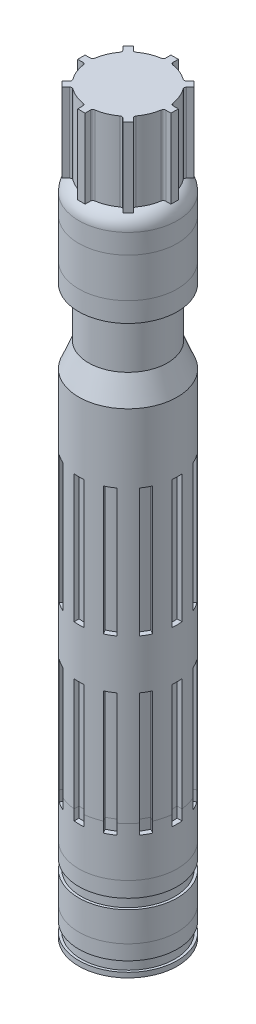
SolidWorks part; units mm, degrees
material "AISI 8620 Steel, carburized"
ref_plane "Front Plane" through (0, 0, 0) normal (1, 0, 0) x (0, 1, 0)
ref_plane "Top Plane" through (0, 0, 0) normal (0, 0, 1) x (0, 1, 0)
ref_plane "Right Plane" through (0, 0, 0) normal (0, 1, 0) x (-1, 0, 0)
sketch "Sketch1" plane through (0, 0, 0) normal (1, 0, 0) x (0, 1, 0)
  line L0 (0, 18.7749) -> (0, 0) construction
  line L1 (-96.0799, 0) -> (122.7259, 0) construction
  line L2 (-70, 0) -> (-70, 10)
  line L3 (-70, 10) -> (30, 10)
  line L4 (70, 8) -> (70, 0) construction
  line L5 (30, 10) -> (30, 0)
  line L6 (35, 8) -> (30, 10)
  line L7 (45, 10) -> (45, 0)
  line L8 (35, 8) -> (45, 8)
  line L9 (45, 10) -> (61, 10)
  line L10 (61, 10) -> (61, 0)
  line L11 (64, 8) -> (70, 8)
  line L12 (64, 8) -> (64, 0)
  line L13 (80, 8) -> (80, 0)
  line L14 (70, 8) -> (80, 8)
  line L15 (-70, 0) -> (80, 0)
  line L16 (-69, 10) -> (-69, 0)
  line L17 (-67, 10) -> (-67, 0)
  line L18 (-58, 10) -> (-58, 0)
  line L19 (-56, 10) -> (-56, 0)
  line L20 (-69, 9.5) -> (-67, 9.5)
  line L21 (-58, 10) -> (-56, 10)
  line L22 (-58, 9.5) -> (-56, 9.5)
  line L23 (35, 8) -> (35, 0)
  arc A0 (61, 10) -> (64, 8) centre (61, 6.75) cw
  dimension "D12" = 3.25
  dimension "D1" = 20
  dimension "D2" = 140
  dimension "D3" = 70
  dimension "D4" = 15
  dimension "D5" = 100
  dimension "D6" = 10
  dimension "D7" = 16
  dimension "D8" = 20
  dimension "D9" = 9
  dimension "D10" = 3
  dimension "D11" = 10
  dimension "D13" = 2
  dimension "D14" = 2
  dimension "D15" = 19
  dimension "D16" = 1
  dimension "D18" = 8
  dimension "D17" = 14
revolve "Revolve1" add sketch "Sketch1" angle 360 about L1 region at (0, -69.5, 5) region at (0, -68, 4.75) region at (0, -62.5, 5) region at (0, -57, 4.75) region at (0, -13, 5) region at (0, 32.4074, 4.5185) region at (0, 40, 4) region at (0, 53, 5) region at (0, 62.4528, 4.7384) region at (0, 72, 4)
sketch "Sketch2" plane through (0, 0, 0) normal (1, 0, 0) x (0, 1, 0)
  line L0 (-13.6637, 0) -> (10.2751, 0) construction
  line L1 (-45, 1) -> (-20, 1)
  line L2 (-45, 1) -> (-45, -1)
  line L3 (-45, -1) -> (-20, -1)
  line L4 (-20, 1) -> (-20, -1)
  line L5 (-70, 10) -> (-70, -10) construction
  line L7 (-10, 1) -> (16, 1)
  line L8 (-10, 1) -> (-10, -1)
  line L9 (-10, -1) -> (16, -1)
  line L10 (16, 1) -> (16, -1)
  dimension "D1" = 25
  dimension "D2" = 25
  dimension "D3" = 2
  dimension "D4" = 1
  dimension "D5" = 2
  dimension "D6" = 10
  dimension "D7" = 26
  dimension "D8" = 1
extrude "Cut-Extrude1" cut sketch "Sketch2" against normal blind 1 from surface starting at face at (0, 30, -10)
pattern_circular "CirPattern1" count 12 over 360 about axis through (0, 30, 0) along (0, -1, 0) of "Cut-Extrude1"
sketch "Sketch3" plane through (0, 80, 0) normal (0, 1, 0) x (-1, 0, 0)
  line L0 (0, 12.9464) -> (0, -12.258) construction
  line L1 (-11.4357, 0) -> (16.9049, 0) construction
  line L3 (6.9496, 0.75) -> (9.46, 0.75)
  line L4 (6.9496, 0.75) -> (6.9496, -0.75)
  line L5 (6.9496, -0.75) -> (9.46, -0.75)
  line L6 (9.46, 0.75) -> (9.46, -0.75)
  point P9 (9.46, 0)
  dimension "D1" = 1.5
  dimension "D2" = 9.46
extrude "Boss-Extrude2" add sketch "Sketch3" against normal blind 16 contours L3 L6 L5 L4
pattern_circular "CirPattern2" count 8 over 360 about axis through (0, 80, 0) along (0, -1, 0) of "Boss-Extrude2"
ref_axis "Axis1" through (0, 45, 0) along (0, -1, 0)
ref_plane "Plane1" through (0, 57, 0) normal (0, 1, 0) x (-1, 0, 0)
ref_plane "Plane2" through (0, 49, 0) normal (0, 1, 0) x (-1, 0, 0)
ref_plane "Plane3" through (0, -42.88, 0) normal (0, 1, 0) x (-1, 0, 0)
ref_plane "Plane4" through (0, -52.88, 0) normal (0, 1, 0) x (-1, 0, 0)
ref_plane "Plane5" through (0, -56, 0) normal (0, 1, 0) x (-1, 0, 0)
ref_plane "Plane6" through (0, -64, 0) normal (0, 1, 0) x (-1, 0, 0)
split line "Split Line2"
fillet "Fillet1" radius 0.5 2 edges at (-7.9648, 72, 0.75) (-7.9648, 72, -0.75)
fillet "Fillet2" radius 0.5 14 edges at (-5.1016, 72, -6.1623) (-6.1623, 72, -5.1016) (-6.1623, 72, 5.1016) (-5.1016, 72, 6.1623) (-0.75, 72, 7.9648) (0.75, 72, 7.9648) (5.1016, 72, 6.1623) (6.1623, 72, 5.1016) (7.9648, 72, 0.75) (7.9648, 72, -0.75) (6.1623, 72, -5.1016) (5.1016, 72, -6.1623) (0.75, 72, -7.9648) (-0.75, 72, -7.9648)
